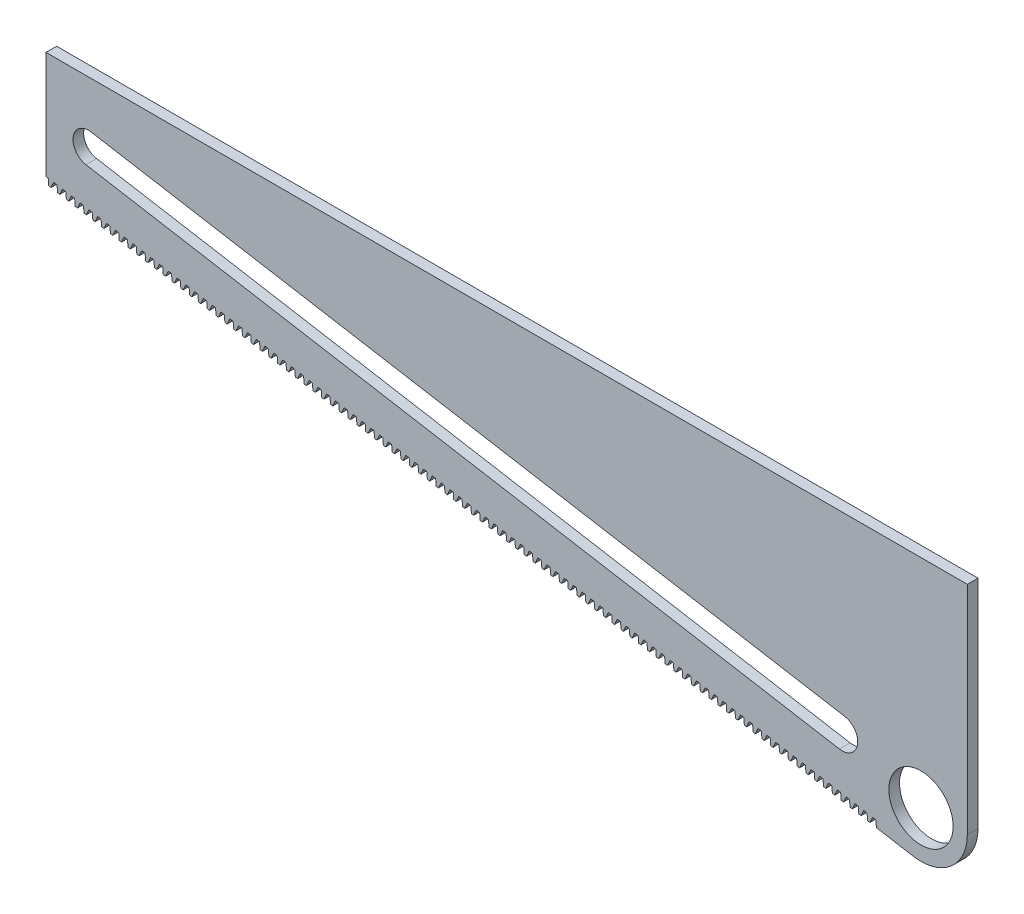
SolidWorks part; units mm, degrees
material "Polypropylene"
ref_plane "Front Plane" through (0, 0, 0) normal (0, 0, 1) x (1, 0, 0)
ref_plane "Top Plane" through (0, 0, 0) normal (0, 1, 0) x (1, 0, 0)
ref_plane "Right Plane" through (0, 0, 0) normal (1, 0, 0) x (0, 0, -1)
sketch "Sketch1" plane through (0, 0, 0) normal (0, 0, 1) x (1, 0, 0)
  line L0 (19.05, 0) -> (19.05, -76.2) construction
  line L1 (0, 19.05) -> (-57.15, 19.05) construction
  line L2 (19.05, -155.575) -> (168.9894, -155.575) construction
  line L3 (0, -95.25) -> (-57.15, -95.25) construction
  line L4 (-57.15, -95.25) -> (-57.15, 19.05) construction
  line L5 (168.9894, 7.239) -> (168.9894, -18.161) construction
  line L6 (168.9894, -18.161) -> (168.9894, -155.575) construction
  line L7 (168.9894, 7.239) -> (143.6189, 6.0141) construction
  line L8 (143.6189, 6.0141) -> (19.05, 0) construction
  line L9 (165.4887, -13.1639) -> (-221.8613, 53.2971)
  line L10 (189.6904, 7.239) -> (189.6904, 104.0971)
  line L12 (197.5644, 110.4886) -> (197.5644, -33.1911) construction
  line L13 (189.6904, 104.0971) -> (-221.8613, 104.0971)
  line L16 (-221.8613, 104.0971) -> (-221.8613, 53.2971)
  line L17 (133.7387, 18.7144) -> (-202.8113, 76.4592) construction
  line L18 (132.5549, 11.8152) -> (-203.9951, 69.5601)
  line L19 (134.9224, 25.6136) -> (-201.6276, 83.3584)
  arc A0 (19.05, 0) -> (0, 19.05) centre (0, 0) ccw construction
  arc A1 (19.05, -76.2) -> (0, -95.25) centre (0, -76.2) cw construction
  circle A2 centre (168.9894, 7.239) radius 14.351
  circle A3 centre (168.9894, 7.239) radius 25.4 construction
  arc A4 (165.4887, -13.1639) -> (189.6904, 7.239) centre (168.9894, 7.239) ccw
  arc A5 (132.5549, 11.8152) -> (134.9224, 25.6136) centre (133.7387, 18.7144) ccw
  arc A6 (-201.6276, 83.3584) -> (-203.9951, 69.5601) centre (-202.8113, 76.4592) ccw
  point P24 (-34.5363, 47.5868)
  point P37 (-98.522, 137.0845)
  dimension "D1" = 19.05
  dimension "D4" = 19.05
  dimension "D6" = 28.702
  dimension "D7" = 50.8
  dimension "D10" = 6.35
  dimension "D13" = 28.575
  dimension "D15" = 7
  dimension "D2" = 155.575
  dimension "D3" = 76.2
  dimension "D5" = 114.3
  dimension "D8" = 137.414
  dimension "D9" = 124.714
  dimension "D11" = 12.5
  dimension "D12" = 387.35
  dimension "D14" = 50.8
  dimension "D16" = 19.05
  dimension "D17" = 19.05
  dimension "D18" = 336.55
  dimension "D19" = 259.6721
extrude "Boss-Extrude1" add sketch "Sketch1" along normal blind 4.7625
sketch "Sketch2" plane through (0, 0, 4.7625) normal (0, 0, 1) x (1, 0, 0)
  line L0 (-220.6224, 53.149) -> (-220.8392, 55.7505)
  line L1 (-221.0914, 56.0256) -> (-222.1159, 56.2014)
  line L2 (-222.4453, 56.0261) -> (-223.517, 53.6456)
  line L3 (-223.5762, 53.5914) -> (-223.5719, 53.6164) construction
  line L4 (-221.6036, 56.1135) -> (-222.0804, 53.3347) construction
  line L5 (-220.5803, 54.3917) -> (-223.1424, 54.8313) construction
  line L6 (-221.8613, 53.2971) -> (165.4887, -13.1639) construction
  line L7 (-222.9946, 54.8059) -> (-223.2471, 53.3347) construction
  line L8 (-220.728, 54.417) -> (-220.9137, 53.3347) construction
  line L11 (-220.5846, 53.0781) -> (-223.5762, 53.5914)
  line L13 (-220.5803, 53.1031) -> (-220.1097, 53.0224)
  line L14 (-220.1097, 53.0224) -> (-220.114, 52.9973)
  line L15 (-220.114, 52.9973) -> (-220.5846, 53.0781)
  line L16 (-220.5846, 53.0781) -> (-220.5803, 53.1031) construction
  line L17 (-224.0425, 53.6972) -> (-224.0468, 53.6721)
  line L18 (-224.0468, 53.6721) -> (-223.5762, 53.5914)
  line L19 (-223.5719, 53.6164) -> (-224.0425, 53.6972)
  line L21 (-221.8613, 104.0971) -> (-221.8613, 53.2971) construction
  arc A0 (-222.1159, 56.2014) -> (-222.4453, 56.0261) centre (-222.1674, 55.901) ccw
  arc A1 (-220.8392, 55.7505) -> (-221.0914, 56.0256) centre (-221.1429, 55.7252) ccw
  arc A2 (-223.5719, 53.6164) -> (-223.517, 53.6456) centre (-223.5633, 53.6665) ccw
  arc A3 (-220.6224, 53.149) -> (-220.5803, 53.1031) centre (-220.5717, 53.1532) ccw
  point P6 (-221.8613, 54.6115)
  dimension "D1" = 0.0254
  dimension "Root_fillet" = 0.3048
  dimension "Break_rad" = 0.0508
  dimension "Gap_width" = 2.2997
  dimension "Dedendum" = 1.524
  dimension "Addendum_plus" = 1.2954
  dimension "Pressure_angle" = 14.5
  dimension "D2" = 0.4775
extrude "Cut-Extrude2" cut sketch "Sketch2" against normal through all
pattern_linear "LPattern2" count 95 spacing 3.9903 along (0.9856, -0.1691, 0) of "Cut-Extrude2"
